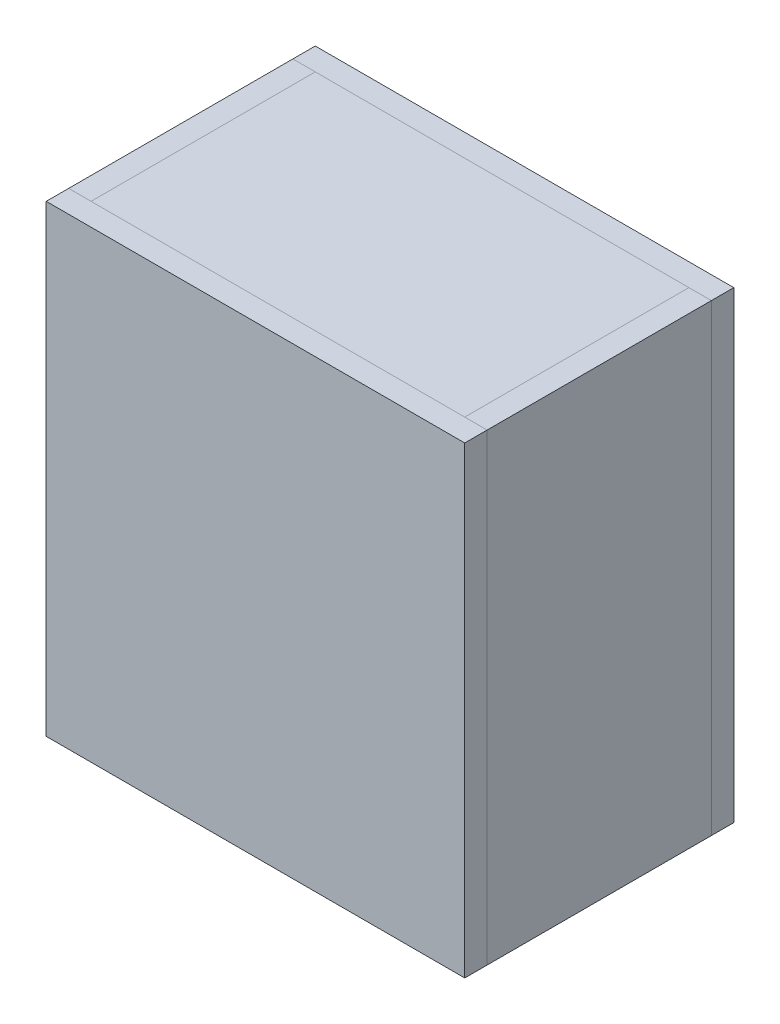
SolidWorks part; units mm, degrees
ref_plane "Alzado" through (0, 0, 0) normal (1, 0, 0) x (0, 1, 0)
ref_plane "Planta" through (0, 0, 0) normal (0, 0, 1) x (0, 1, 0)
ref_plane "Vista lateral" through (0, 0, 0) normal (0, 1, 0) x (-1, 0, 0)
sketch "Croquis3" plane through (0, 0, 0) normal (0, 0, 1) x (0, 1, 0)
  line L1 (0, 0) -> (310, 0)
  line L2 (0, 0) -> (0, 280)
  line L3 (0, 280) -> (310, 280)
  line L4 (310, 0) -> (310, 280)
  dimension "D1" = 280
  dimension "D2" = 310
extrude "Saliente-Extruir1" add sketch "Croquis3" along normal blind 15
sketch "Croquis4" plane through (0, 0, 15) normal (0, 0, 1) x (1, 0, 0)
  line L0 (-280, 295) -> (0, 295)
  line L1 (-280, 310) -> (-265, 310)
  line L2 (-280, 310) -> (-280, 0)
  line L3 (-280, 0) -> (-265, 0)
  line L4 (-280, 0) -> (0, 0)
  line L5 (0, 0) -> (0, 310)
  line L6 (0, 310) -> (-280, 310)
  line L7 (-280, 310) -> (-280, 0)
  line L8 (-280, 0) -> (0, 0)
  line L9 (0, 0) -> (0, 310)
  line L10 (0, 310) -> (-280, 310)
  line L11 (-280, 310) -> (-280, 0)
  line L12 (-265, 310) -> (-265, 0)
  line L13 (0, 310) -> (-15, 310)
  line L14 (0, 310) -> (0, 0)
  line L15 (0, 0) -> (-15, 0)
  line L16 (-15, 310) -> (-15, 0)
  line L17 (-280, 15) -> (0, 15)
  line M10 (-280, 0) -> (0, 0)
  line M11 (0, 0) -> (0, 310)
  line M12 (0, 310) -> (-280, 310)
  line M13 (-280, 310) -> (-280, 0)
  dimension "D2" = 15
  dimension "D3" = 15
  dimension "D4" = 15
  dimension "D5" = 15
  dimension "D1" = 0
extrude "Saliente-Extruir2" add sketch "Croquis4" along normal blind 150 separate body contours L17 L12 L0 M13 | L16 L17 L14 L0 | L12 L0 M12 M13 | L16 L0 M12 M11 | L17 L11 L12 M10 | L17 L16 L8 M11 region at (-272.5, 302.5, 15) region at (-272.5, 155, 15) region at (-272.5, 7.5, 15) region at (-7.5, 302.5, 15) region at (-7.5, 155, 15) region at (-7.5, 7.5, 15)
extrude "Saliente-Extruir3" add sketch "Croquis4<3>" along normal blind 150 separate body contours L16 L10 L12 L0 | L17 L12 L16 M10 region at (-140, 302.5, 15) region at (-140, 7.5, 15)
sketch "Croquis4<3>" plane through (0, 0, 15) normal (0, 0, 1) x (1, 0, 0) same geometry as "Croquis4"
sketch "Croquis5" plane through (0, 0, 165) normal (0, 0, 1) x (1, 0, 0)
  line L0 (-15, 0) -> (0, 0) construction
  line L1 (0, 0) -> (0, 310) construction
  line L2 (-265, 0) -> (-15, 0) construction
  line L3 (-280, 0) -> (-265, 0) construction
  line L4 (0, 310) -> (-15, 310) construction
  line L5 (-265, 310) -> (-280, 310) construction
  line L6 (-15, 310) -> (-265, 310) construction
  line L7 (-280, 310) -> (-280, 0) construction
  line L8 (-15, 0) -> (0, 0)
  line L9 (0, 0) -> (0, 310)
  line L10 (-265, 0) -> (-15, 0)
  line L11 (-280, 0) -> (-265, 0)
  line L12 (0, 310) -> (-15, 310)
  line L13 (-265, 310) -> (-280, 310)
  line L14 (-15, 310) -> (-265, 310)
  line L15 (-280, 310) -> (-280, 0)
extrude "Saliente-Extruir4" add sketch "Croquis5" along normal blind 15 separate body
sketch "Croquis7" plane through (-15, 0, 0) normal (-1, 0, 0) x (0, -1, 0)
  line L0 (-295, 165) -> (-295, 15) construction
  line L1 (-295, 165) -> (-295, 15)
  line L2 (-310, 165) -> (0, 165) construction
  line L3 (-267.0211, 115) -> (-47.0211, 115)
  line L4 (-310, 15) -> (0, 15)
  line L5 (0, 15) -> (0, 165)
  line L6 (0, 165) -> (-310, 165)
  line L7 (-310, 165) -> (-310, 15)
  line L8 (-310, 15) -> (0, 15)
  line L9 (0, 15) -> (0, 165)
  line L10 (0, 165) -> (-310, 165)
  line L11 (-310, 165) -> (-310, 15)
  line L12 (-267.0211, 115) -> (-267.0211, 105)
  line L13 (-267.0211, 105) -> (-47.0211, 105)
  line L14 (-47.0211, 115) -> (-47.0211, 105)
  line L15 (-267.0211, 55) -> (-50.335, 55)
  line L16 (-267.0211, 55) -> (-267.0211, 45)
  line L17 (-267.0211, 45) -> (-50.335, 45)
  line L18 (-50.335, 55) -> (-50.335, 45)
  point P16 (-267.0211, 115)
  dimension "D2" = 10
  dimension "D3" = 220
  dimension "D4" = 50
  dimension "D5" = 50
  dimension "D1" = 0
extrude "Saliente-Extruir5" add sketch "Croquis7" along normal blind 167 contours L14 L3 L12 L13 | L18 L15 L16 L17 region at (-15, 157.0211, 110) region at (-15, 158.678, 50)
